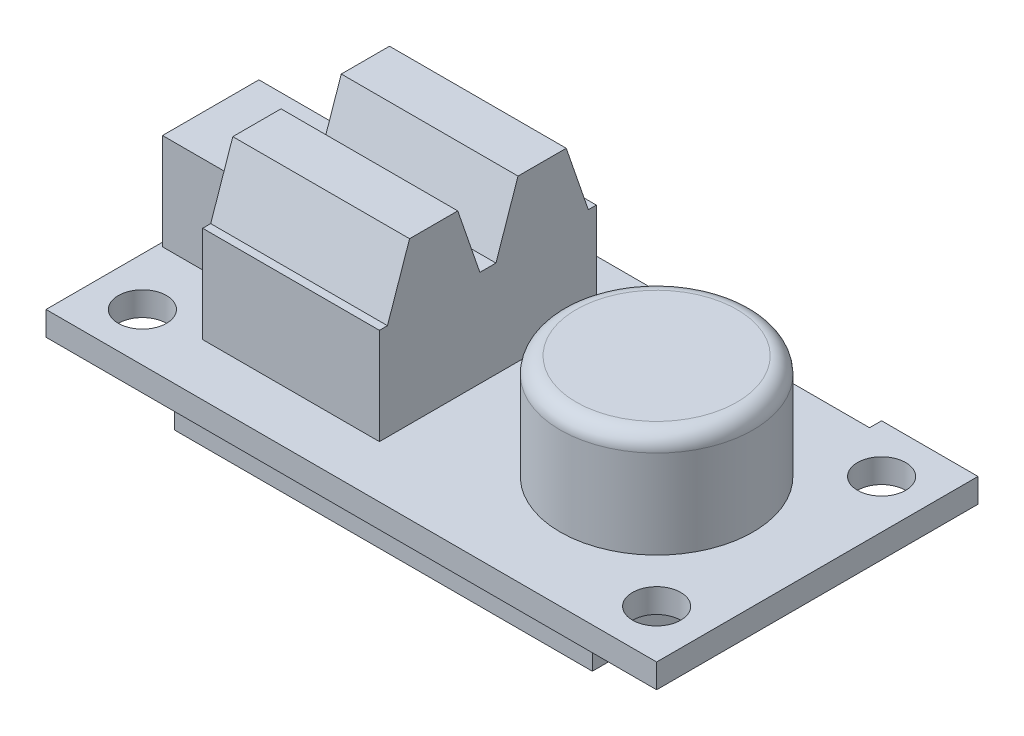
SolidWorks part; units mm, degrees
ref_plane "Front Plane" through (0, 0, 0) normal (0, 0, 1) x (1, 0, 0)
ref_plane "Top Plane" through (0, 0, 0) normal (0, 1, 0) x (1, 0, 0)
ref_plane "Right Plane" through (0, 0, 0) normal (1, 0, 0) x (0, 0, -1)
sketch "Sketch1" plane through (0, 0, 0) normal (0, 1, 0) x (1, 0, 0)
  line L0 (-16, 7) -> (16, 7) construction
  line L1 (-19, -10) -> (19, -10)
  line L2 (-19, -10) -> (-19, 10)
  line L3 (-19, 10) -> (1, 10)
  line L4 (19, -10) -> (19, 10)
  line L5 (-19, -10) -> (19, 10) construction
  line L6 (-19, 10) -> (19, -10) construction
  line L7 (16, 7) -> (16, -7) construction
  line L8 (16, -7) -> (-16, -7) construction
  line L9 (-16, -7) -> (-16, 7) construction
  line L10 (13, 10) -> (13, 9.25)
  line L11 (13, 9.25) -> (1, 9.25)
  line L12 (1, 9.25) -> (1, 10)
  line L13 (1, 10) -> (13, 10) construction
  line L14 (13, 10) -> (19, 10)
  circle A0 centre (-16, 7) radius 1.5
  circle A1 centre (-16, -7) radius 1.5
  circle A2 centre (16, -7) radius 1.5
  circle A3 centre (16, 7) radius 1.5
  point P0 (0, 0)
  point P14 (0, 7)
  point P15 (0, -7)
  point P16 (-16, 0)
  point P17 (16, 0)
  dimension "D3" = 3
  dimension "D1" = 20
  dimension "D2" = 38
  dimension "D4" = 3
  dimension "D5" = 3
  dimension "D6" = 6
  dimension "D7" = 12
  dimension "D8" = 0.75
extrude "Boss-Extrude1" add sketch "Sketch1" along normal blind 1.5
sketch "Sketch2" plane through (0, 1.5, 0) normal (0, 1, 0) x (1, 0, 0)
  line L0 (19, -10) -> (19, 10) construction
  circle A0 centre (9, 0) radius 6
  point P4 (0, 0)
  dimension "D2" = 12
  dimension "D1" = 10
extrude "Boss-Extrude2" add sketch "Sketch2" along normal blind 6.5
fillet "Fillet1" radius 1 1 edges at (9, 8, 6)
sketch "Sketch3" plane through (0, 1.5, 0) normal (0, 1, 0) x (1, 0, 0)
  line L1 (-18.75, 3) -> (-13.75, 3)
  line L2 (-18.75, 3) -> (-18.75, -3)
  line L3 (-18.75, -3) -> (-13.75, -3)
  line L4 (-13.75, 3) -> (-13.75, -3)
  line L5 (-18.75, 3) -> (-13.75, -3) construction
  line L6 (-18.75, -3) -> (-13.75, 3) construction
  line L7 (-4.4, 0) -> (4.4, 0) construction
  line L8 (-19, 10) -> (-19, -10) construction
  point P0 (-16.25, 0)
  point P5 (0, 0)
  point P6 (-16.1457, 0)
  dimension "D1" = 5
  dimension "D2" = 6
  dimension "D3" = 0.25
extrude "Boss-Extrude3" add sketch "Sketch3" along normal blind 6
sketch "Sketch5" plane through (0, 0, 0) normal (1, 0, 0) x (0, 0, -1)
  line L0 (6.75, 1.5) -> (6.75, 7.5)
  line L1 (0, 7.5) -> (0, 1.5) construction
  line L2 (6.75, 7.5) -> (6.25, 7.5)
  line L3 (6.25, 7.5) -> (4.875, 11.5)
  line L4 (4.875, 11.5) -> (1.875, 11.5)
  line L5 (1.875, 11.5) -> (0.5, 7.5)
  line L6 (0.5, 7.5) -> (-0.5, 7.5)
  line L7 (-0.5, 7.5) -> (-1.875, 11.5)
  line L8 (-1.875, 11.5) -> (-4.875, 11.5)
  line L9 (-4.875, 11.5) -> (-6.25, 7.5)
  line L10 (-6.25, 7.5) -> (-6.75, 7.5)
  line L11 (-6.75, 7.5) -> (-6.75, 1.5)
  line L12 (-6.75, 1.5) -> (6.75, 1.5)
  line L13 (10, 1.5) -> (-10, 1.5) construction
  line L15 (-1.875, 11.5) -> (1.875, 11.5) construction
  point P2 (0, 11.5)
  point P4 (0, 7.5)
  point P16 (0, 1.5)
  point P20 (3.375, 11.5)
  dimension "D1" = 3
  dimension "D2" = 13.5
  dimension "D3" = 0.5
  dimension "D4" = 0.5
  dimension "D5" = 1
  dimension "D6" = 6
  dimension "D7" = 4
extrude "Boss-Extrude4" add sketch "Sketch5" along normal blind 11 from offset 12.5 offset against normal yes
sketch "Sketch6" plane through (0, 0, 0) normal (0, -1, 0) x (1, 0, 0)
  line L1 (-13, -8) -> (13, -8)
  line L2 (-13, -8) -> (-13, 8)
  line L3 (-13, 8) -> (13, 8)
  line L4 (13, -8) -> (13, 8)
  line L5 (-13, -8) -> (13, 8) construction
  line L6 (-13, 8) -> (13, -8) construction
  point P0 (0, 0)
  dimension "D1" = 16
  dimension "D2" = 26
extrude "Boss-Extrude5" add sketch "Sketch6" along normal blind 3
